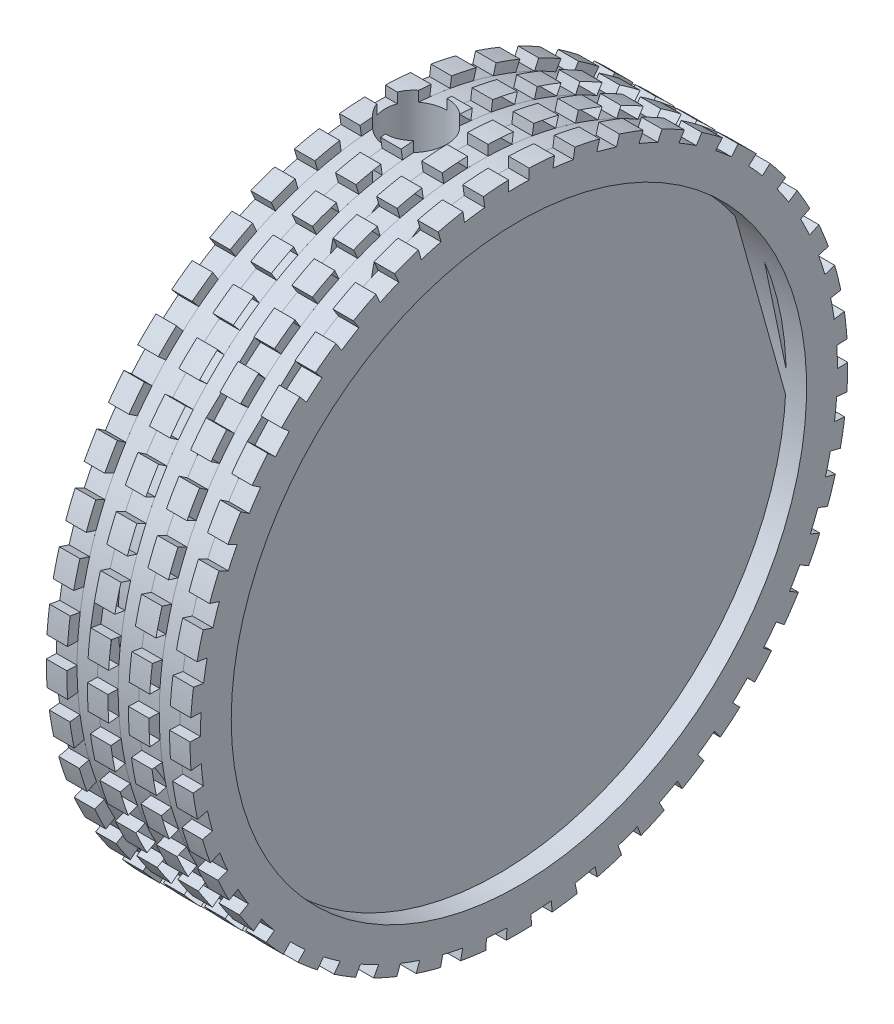
SolidWorks part; units mm, degrees
ref_plane "Front Plane" through (0, 0, 0) normal (0, 0, 1) x (1, 0, 0)
ref_plane "Top Plane" through (0, 0, 0) normal (0, 1, 0) x (1, 0, 0)
ref_plane "Right Plane" through (0, 0, 0) normal (1, 0, 0) x (0, 0, -1)
sketch "Sketch1" plane through (0, 0, 0) normal (0, 0, 1) x (1, 0, 0)
  line L0 (7, 14) -> (7, 16)
  line L1 (0, 2) -> (5, 2)
  line L2 (0, 2) -> (0, 16)
  line L3 (0, 16) -> (7, 16)
  line L4 (5, 2) -> (5, 4)
  line L5 (7, 14) -> (4, 14)
  line L7 (5, 4) -> (4, 4)
  line L8 (4, 14) -> (4, 4)
  line L9 (0, 0) -> (22.7949, 0) construction
  dimension "D1" = 7
  dimension "D2" = 4
  dimension "D3" = 5
  dimension "D4" = 4
  dimension "D5" = 8
  dimension "D6" = 28
  dimension "D7" = 32
revolve "Revolve1" add sketch "Sketch1" angle 360 about L9
sketch "Sketch2" plane through (0, 0, 0) normal (0, 0, 1) x (1, 0, 0)
  line L0 (2, 0) -> (2, 16)
  line L1 (2, 0) -> (2.9, 0)
  line L2 (2.9, 0) -> (2.9, 11.5)
  line L3 (2.9, 11.5) -> (3.5, 11.5)
  line L4 (3.5, 11.5) -> (3.5, 16)
  line L5 (7, 16) -> (0, 16) construction
  line L6 (0, 0) -> (7, 0) construction
  line L7 (7, -16) -> (7, 16) construction
  line L8 (2, 16) -> (3.5, 16)
  dimension "D1" = 2
  dimension "D2" = 0.9
  dimension "D3" = 4.5
  dimension "D4" = 1.5
revolve "Cut-Revolve1" cut sketch "Sketch2" angle 360 about L0
sketch "Sketch3" plane through (0, 0, 0) normal (0, 0, 1) x (1, 0, 0)
  line L0 (7, 16) -> (3.4999, 16) construction
  line L1 (6, 16) -> (5, 16)
  line L2 (6, 16) -> (6, 15.5)
  line L3 (6, 15.5) -> (5, 15.5)
  line L4 (5, 16) -> (5, 15.5)
  line L5 (7, -16) -> (7, 16) construction
  dimension "D1" = 1
  dimension "D2" = 0.5
  dimension "D3" = 1
revolve "Cut-Revolve2" cut sketch "Sketch3" angle 360 about L9
sketch "Sketch4" plane through (0, 0, 0) normal (1, 0, 0) x (0, 0, -1)
  line L2 (0.5, 15.4922) -> (0.5, 15.9922)
  line L4 (-0.5, 15.4922) -> (-0.5, 15.9922)
  circle A0 centre (0, 0) radius 16 construction
  arc A1 (0.5, 15.4922) -> (-0.5, 15.4922) centre (0, 0) ccw
  arc A2 (0.5, 15.9922) -> (-0.5, 15.9922) centre (0, 0) ccw
  point P5 (0, 0)
  point P6 (-1.7042, 15.909)
  point P7 (0.6079, 15.9884)
  point P8 (0, 16)
  dimension "D2" = 0.5
  dimension "D1" = 1
extrude "Cut-Extrude1" cut sketch "Sketch4" along normal through all
pattern_linear "LPattern1" count 3 spacing 2 along (-1, 0, 0) of "Cut-Revolve2"
pattern_circular "CirPattern1" count 45 over 360 about axis through (0, 0, 0) along (1, 0, 0) of "Cut-Extrude1"
sketch "Sketch5" plane through (4, 0, 0) normal (1, 0, 0) x (0, 0, -1)
  line L0 (7.3473, -10.1127) -> (2.9389, -4.0451)
  line L1 (-3.7735, -3.2803) -> (-9.4339, -8.2007)
  line L2 (0, 0) -> (11.7834, 0) construction
  arc A0 (-9.4339, -8.2007) -> (7.3473, -10.1127) centre (0, 0) ccw
  arc A1 (-3.7735, -3.2803) -> (2.9389, -4.0451) centre (0, 0) ccw
  dimension "D1" = 5
  dimension "D2" = 12.5
  dimension "D3" = 85
  dimension "D4" = 54
extrude "Cut-Extrude3" cut sketch "Sketch5" against normal through all
fillet "Fillet1" radius 1 4 edges at (2, -10.1127, -7.3473) (2, -4.0451, -2.9389) (2, -3.2803, 3.7735) (2, -8.2007, 9.4339)
pattern_circular "CirPattern3" count 3 every 116 about axis through (0, 0, 0) along (1, 0, 0) of "Cut-Extrude3", "Fillet1"
